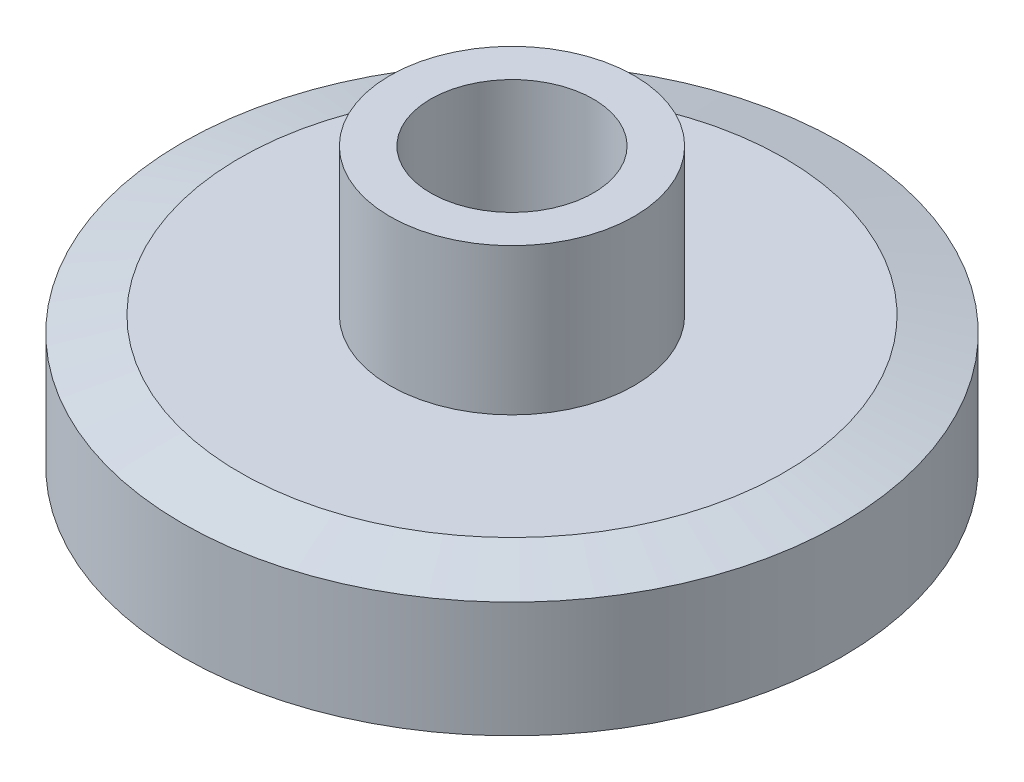
SolidWorks part; units mm, degrees
material "Сталь ШХ15 ГОСТ 801-78"
ref_plane "Plane1" through (0, 0, 0) normal (0, 0, 1) x (1, 0, 0)
ref_plane "Plane2" through (0, 0, 0) normal (0, 1, 0) x (1, 0, 0)
ref_plane "Plane3" through (0, 0, 0) normal (1, 0, 0) x (0, 0, -1)
sketch "Эскиз2" plane through (0, 0, 0) normal (0, 0, 1) x (1, 0, 0)
  line L0 (0, 0) -> (8.1, 0)
  line L1 (8.1, 0) -> (8.1, 3.6)
  line L2 (8.1, 3.6) -> (3, 3.6)
  line L3 (3, 3.6) -> (3, 7.2)
  line L4 (3, 7.2) -> (0, 7.2)
  line L5 (0, 7.2) -> (0, 0)
  dimension "D1" = 8.1
  dimension "D2" = 3.6
  dimension "3.6" = 3.6
  dimension "D4" = 3
ref_axis "Ось1" through (0, 7.2, 0) along (0, -1, 0)
revolve "Повернуть2" add sketch "Эскиз2" angle 360 about axis through (0, 7.2, 0) along (0, -1, 0)
chamfer "Фаска2" distance 1.41 angle 15 1 edges at (0, 3.6, 8.1) first distance on face at (0, 3.6, 3)
chamfer "Фаска3" distance 1.41 angle 15 1 edges at (0, 0, 8.1) first distance on face at (0, 0, 8.1)
sketch "Эскиз4" plane through (0, 7.2, 0) normal (0, 1, 0) x (1, 0, 0)
  circle A0 centre (0, 0) radius 2
  dimension "D1" = 4
extrude "Вырез-Вытянуть2" cut sketch "Эскиз4" against normal through all both contours A0
